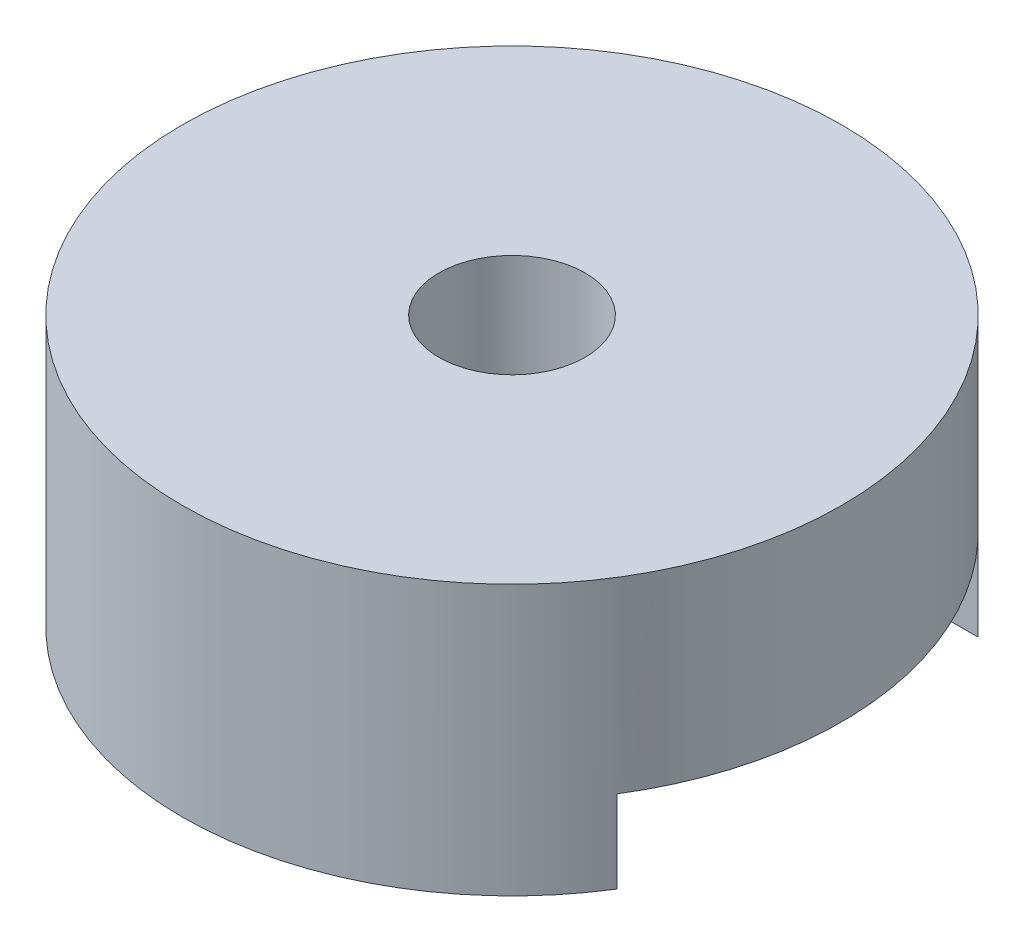
SolidWorks part; units mm, degrees
ref_plane "Front Plane" through (0, 0, 0) normal (0, 0, 1) x (1, 0, 0)
ref_plane "Top Plane" through (0, 0, 0) normal (0, 1, 0) x (1, 0, 0)
ref_plane "Right Plane" through (0, 0, 0) normal (1, 0, 0) x (0, 0, -1)
sketch "Sketch1" plane through (0, 0, 0) normal (0, 1, 0) x (1, 0, 0)
  line L0 (-7.9, 8.075) -> (7.9, 8.075)
  line L1 (-6.1, 6.275) -> (6.1, 6.275)
  line L2 (-6.1, 6.275) -> (-6.1, -6.275)
  line L3 (-6.1, -6.275) -> (6.1, -6.275)
  line L4 (6.1, 6.275) -> (6.1, -6.275)
  line L5 (-6.1, 6.275) -> (6.1, -6.275) construction
  line L6 (-6.1, -6.275) -> (6.1, 6.275) construction
  line L7 (7.9, 8.075) -> (7.9, -8.075)
  line L8 (-7.9, -8.075) -> (7.9, -8.075)
  line L9 (-7.9, 8.075) -> (-7.9, -8.075)
  line L11 (-15.6, 10.875) -> (10.7, 10.875)
  line L12 (-15.6, 10.875) -> (-15.6, -8.475)
  line L13 (-15.6, -8.475) -> (10.7, -8.475)
  line L14 (10.7, 10.875) -> (10.7, -8.475)
  circle A0 centre (0, 0) radius 3.55
  circle A1 centre (0, 0) radius 16
  dimension "D1" = 7.1
  dimension "D9" = 32
  dimension "D2" = 12.2
  dimension "D3" = 12.55
  dimension "D5" = 2.8
  dimension "D6" = 7.7
  dimension "D7" = 0.4
  dimension "D8" = 2.8
  dimension "D4" = 1.8
extrude "Boss-Extrude1" add sketch "Sketch1" against normal blind 3 contours L0 L9 L8 L7 L1 L4 L3 L2 region at (0, 0, -7.8491)
extrude "Boss-Extrude2" add sketch "Sketch1<3>" against normal blind 5 contours L11 A1 L12 L13 L14 L9 L0 L7 L8 | L12 A1 region at (-0.518, 0, -10.5485) region at (-15.7602, 0, 0)
sketch "Sketch1<3>" plane through (0, 0, 0) normal (0, 1, 0) x (1, 0, 0) same geometry as "Sketch1"
extrude "Boss-Extrude3" add sketch "Sketch1<4>" against normal blind 6.6 contours L13 A1 L11 L14 region at (5.6815, 0, -14.4903)
sketch "Sketch1<4>" plane through (0, 0, 0) normal (0, 1, 0) x (1, 0, 0) same geometry as "Sketch1"
extrude "Boss-Extrude4" add sketch "Sketch1<5>" along normal blind 6.5 contours L4 L1 L2 L3 A0 | L0 L9 L8 L7 L1 L4 L3 L2 | L11 A1 L12 L13 L14 L9 L0 L7 L8 | L13 A1 L11 L14 | L12 A1 region at (0, 0, -7.8491) region at (0, 0, -6.1) region at (5.6815, 0, -14.4903) region at (-0.518, 0, -10.5485) region at (-15.7602, 0, 0)
sketch "Sketch1<5>" plane through (0, 0, 0) normal (0, 1, 0) x (1, 0, 0) same geometry as "Sketch1"
sketch "Sketch2" plane through (0, -6.6, 0) normal (0, -1, 0) x (1, 0, 0)
  line L0 (0, 16.9347) -> (0, -18.5495) construction
  line L1 (-23.2029, 0) -> (24.6052, 0) construction
  circle A0 centre (0, 14) radius 1.225
  circle A1 centre (0, -14) radius 1.225
  dimension "D2" = 2.45
  dimension "D1" = 14
extrude "Cut-Extrude1" cut sketch "Sketch2" against normal blind 12
sketch "Sketch3" plane through (0, -6.6, 0) normal (0, -1, 0) x (1, 0, 0)
  line L0 (-11.736, -10.875) -> (-11.736, 10.875)
  arc A0 (-11.736, -10.875) -> (-13.5711, 8.475) centre (0, 0) ccw construction
  arc A1 (-13.5711, 8.475) -> (-11.736, -10.875) centre (0, 0) ccw construction
  arc A2 (-13.5711, 8.475) -> (-11.736, -10.875) centre (0, 0) ccw
  arc A3 (-11.736, 10.875) -> (-13.5711, 8.475) centre (0, 0) ccw
extrude "Cut-Extrude2" cut sketch "Sketch3" against normal offset from surface (4.6 mm away) 3 up to face at (0, -5, 0)
sketch "Sketch4" plane through (0, -6.6, 0) normal (0, -1, 0) x (1, 0, 0)
  line L0 (10.7, 8.475) -> (13.5711, 8.475)
  line L1 (10.7, -10.875) -> (11.736, -10.875)
  line L2 (10.7, -10.875) -> (10.7, 8.475) construction
  line L3 (10.7, -10.875) -> (10.7, 8.475)
  arc A0 (-11.736, -10.875) -> (-11.736, 10.875) centre (0, 0) ccw construction
  arc A1 (11.736, -10.875) -> (13.5711, 8.475) centre (0, 0) ccw
extrude "Cut-Extrude3" cut sketch "Sketch4" against normal blind 4
sketch "Sketch5" plane through (0, -2, 0) normal (0, -1, 0) x (1, 0, 0)
  line L0 (-13.736, 8.205) -> (-13.736, -8.205) construction
  line L1 (0, 0) -> (-21.2286, -0.0601) construction
  line L2 (-11.736, -10.875) -> (-11.736, 10.875) construction
  arc A0 (-11.736, 10.875) -> (-11.736, -10.875) centre (0, 0) ccw construction
  circle A1 centre (-13.736, 5.0411) radius 0.5
  circle A2 centre (-13.736, 2.5011) radius 0.5
  circle A3 centre (-13.736, -0.0389) radius 0.5
  circle A4 centre (-13.736, -2.5789) radius 0.5
  circle A5 centre (-13.736, -5.1189) radius 0.5
  dimension "D2" = 1
  dimension "D3" = 2
  dimension "D1" = 5
extrude "Cut-Extrude4" cut sketch "Sketch5" against normal blind 0.4
